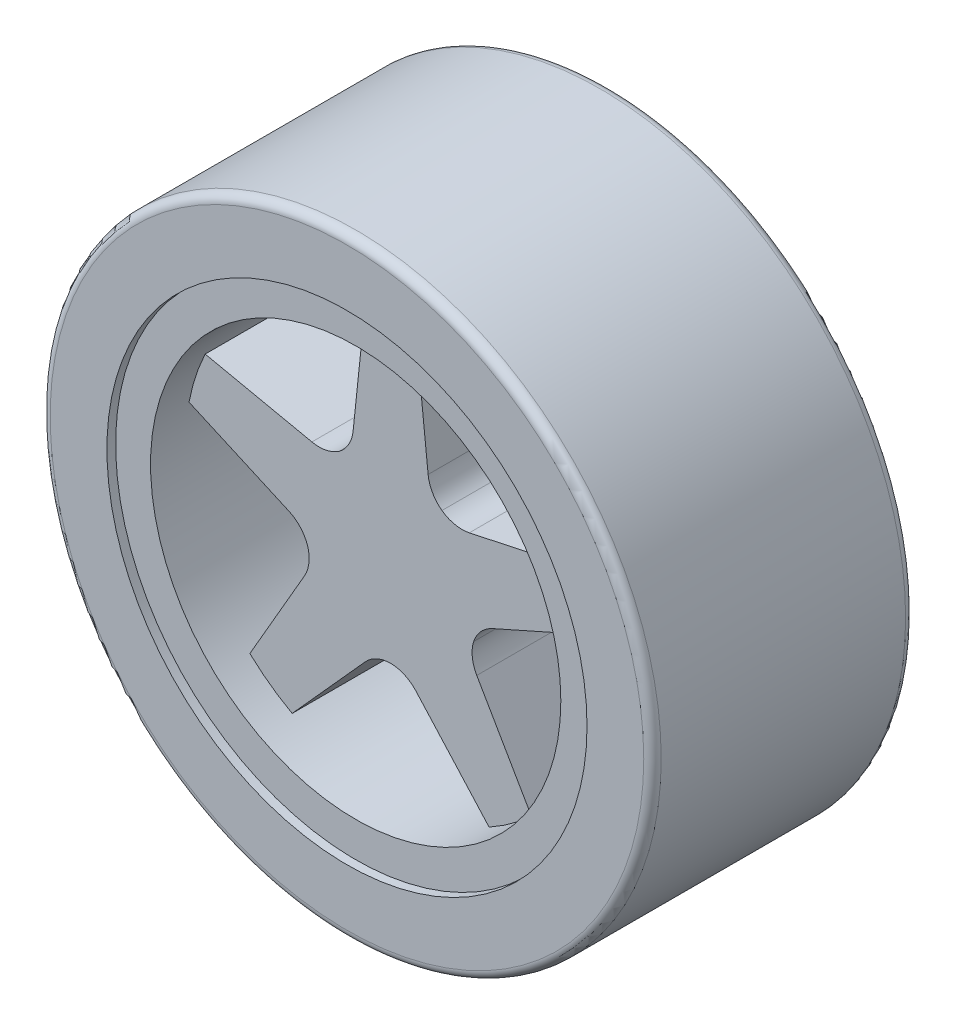
SolidWorks part; units mm, degrees
ref_plane "Front Plane" through (0, 0, 0) normal (0, 0, 1) x (1, 0, 0)
ref_plane "Top Plane" through (0, 0, 0) normal (0, 1, 0) x (1, 0, 0)
ref_plane "Right Plane" through (0, 0, 0) normal (1, 0, 0) x (0, 0, -1)
sketch "Sketch2" plane through (0, 0, 0) normal (0, 0, 1) x (1, 0, 0)
  circle A0 centre (0, 0) radius 35
  circle A1 centre (0, 0) radius 27.5
  dimension "D1" = 70
  dimension "D2" = 55
extrude "Boss-Extrude2" add sketch "Sketch2" along normal mid plane 30
fillet "Fillet2" radius 1 2 edges at (35, 0, -15) (35, 0, 15)
sketch "Sketch4" plane through (0, 0, 0) normal (0, 0, 1) x (1, 0, 0)
  circle A0 centre (0, 0) radius 27.5
  circle A1 centre (0, 0) radius 27.5 construction
  circle A2 centre (0, 0) radius 23.5
  dimension "D1" = 4
extrude "Boss-Extrude4" add sketch "Sketch4" along normal mid plane 28
sketch "Sketch5" plane through (0, 0, 0) normal (0, 0, 1) x (1, 0, 0)
  line L0 (0, 0) -> (0, 23.5) construction
  line L1 (-2.9939, 23.3085) -> (-4.5, 8.9303)
  line L2 (2.9939, 23.3085) -> (4.5, 8.9303)
  arc A0 (-4.5, 8.9303) -> (4.5, 8.9303) centre (0, 0) ccw
  circle A1 centre (0, 0) radius 23.5 construction
  arc A2 (-2.9939, 23.3085) -> (2.9939, 23.3085) centre (0, 0) cw
  point P12 (0, 0)
  dimension "D5" = 20
  dimension "D1" = 3
  dimension "D2" = 3
  dimension "D3" = 4.5
  dimension "D4" = 4.5
extrude "Boss-Extrude5" add sketch "Sketch5" along normal mid plane 20
pattern_circular "CirPattern1" count 5 over 360 about axis through (0, 0, 14) along (0, 0, -1) of "Boss-Extrude5"
fillet "Fillet3" radius 4 10 edges at (-4.5, 8.9303, 0) (-7.1026, 7.0394, 0) (-8.8897, -4.5797, 0) (-9.8838, -1.5201, 0) (1.6085, -9.8698, 0) (-1.6085, -9.8698, 0) (9.8838, -1.5201, 0) (8.8897, -4.5797, 0) (7.1026, 7.0394, 0) (4.5, 8.9303, 0)
